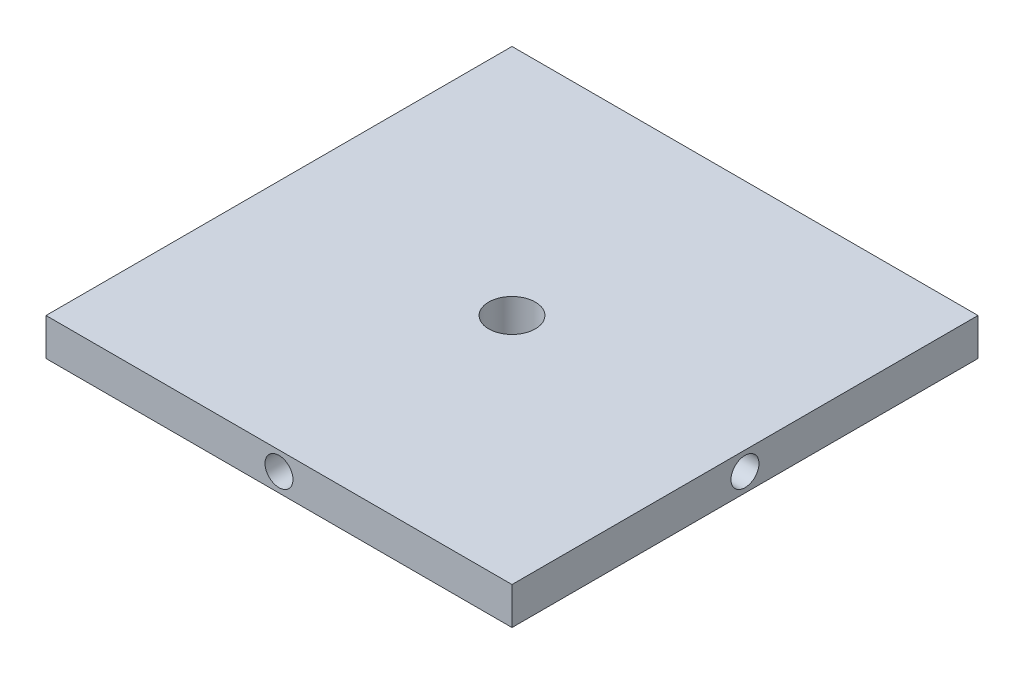
SolidWorks part; units mm, degrees
material "6061-T6 (SS)"
ref_plane "Front Plane" through (0, 0, 0) normal (0, 0, 1) x (1, 0, 0)
ref_plane "Top Plane" through (0, 0, 0) normal (0, 1, 0) x (1, 0, 0)
ref_plane "Right Plane" through (0, 0, 0) normal (1, 0, 0) x (0, 0, -1)
ref_plane "Plane1" through (0, 12.7, 0) normal (0, 1, 0) x (1, 0, 0)
sketch "Sketch1" plane through (0, 0, 0) normal (0, 1, 0) x (1, 0, 0)
  line L1 (-158.75, -158.75) -> (158.75, -158.75)
  line L2 (-158.75, -158.75) -> (-158.75, 158.75)
  line L3 (-158.75, 158.75) -> (158.75, 158.75)
  line L4 (158.75, -158.75) -> (158.75, 158.75)
  line L5 (-158.75, -158.75) -> (158.75, 158.75) construction
  line L6 (-158.75, 158.75) -> (158.75, -158.75) construction
  circle A0 centre (0, 0) radius 15.875
  point P0 (0, 0)
  dimension "D3" = 31.75
  dimension "D1" = 317.5
  dimension "D2" = 317.5
extrude "Boss-Extrude1" add sketch "Sketch1" along normal blind 25.4
ref_axis "Axis1" through (0, 12.7, -265.43) along (0, 0, 1)
ref_axis "Axis2" through (265.43, 12.7, 0) along (-1, 0, 0)
hole_wizard "3/4 (0.75) Diameter Hole2" positions "Sketch4" profile "Sketch5" hole size "3/4" standard "ANSI Inch"
sketch "Sketch4" plane through (158.75, 0, 0) normal (1, 0, 0) x (0, 0, -1)
  point P0 (0, 12.7)
sketch "Sketch5" plane through (158.75, 12.7, 0) normal (0, 1, 0) x (0, 0, -1)
  line L0 (0, 0) -> (0, 81.9232)
  line L1 (0, 81.9232) -> (9.525, 76.2)
  line L2 (9.525, 76.2) -> (9.525, 0)
  line L5 (9.525, 0) -> (0, 0)
  line L10 (0, 81.9232) -> (-9.525, 76.2) construction
  line L11 (0, -6.35) -> (0, 107.95) construction
  dimension "Hole Dia." = 19.05
  dimension "Hole Depth" = 76.2
  dimension "Drill Angle" = 118
hole_wizard "3/4 (0.75) Diameter Hole1" positions "Sketch2" profile "Sketch3" hole size "3/4" standard "ANSI Inch"
sketch "Sketch2" plane through (0, 0, 158.75) normal (0, 0, 1) x (1, 0, 0)
  point P0 (0, 12.7)
sketch "Sketch3" plane through (0, 12.7, 158.75) normal (1, 0, 0) x (0, -1, 0)
  line L0 (0, 0) -> (0, 81.9232)
  line L1 (0, 81.9232) -> (9.525, 76.2)
  line L2 (9.525, 76.2) -> (9.525, 0)
  line L5 (9.525, 0) -> (0, 0)
  line L10 (0, 81.9232) -> (-9.525, 76.2) construction
  line L11 (0, -6.35) -> (0, 107.95) construction
  dimension "Hole Dia." = 19.05
  dimension "Hole Depth" = 76.2
  dimension "Drill Angle" = 118
